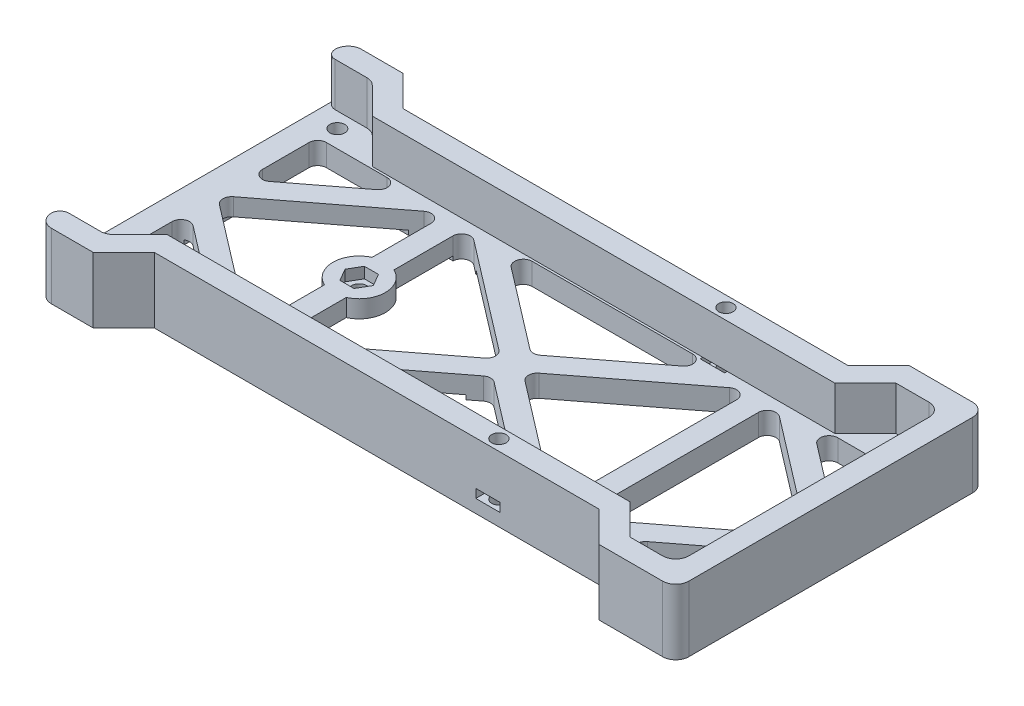
SolidWorks part; units mm, degrees
material "ABS PC"
ref_plane "Front Plane" through (0, 0, 0) normal (0, 0, 1) x (1, 0, 0)
ref_plane "Top Plane" through (0, 0, 0) normal (0, 1, 0) x (1, 0, 0)
ref_plane "Right Plane" through (0, 0, 0) normal (1, 0, 0) x (0, 0, -1)
sketch "Sketch1" plane through (0, 0, 0) normal (0, 1, 0) x (1, 0, 0)
  line L1 (73, -35.5) -> (-73, -35.5)
  line L2 (73, -35.5) -> (73, 35.5)
  line L3 (73, 35.5) -> (-73, 35.5)
  line L4 (-73, -35.5) -> (-73, 35.5)
  line L5 (73, -35.5) -> (-73, 35.5) construction
  line L6 (73, 35.5) -> (-73, -35.5) construction
  point P0 (0, 0)
  dimension "D1" = 146
  dimension "D2" = 71
extrude "Boss-Extrude1" add sketch "Sketch1" along normal blind 15
shell "Shell1" thickness 5 removed face at (0, 15, 0)
sketch "Sketch2" plane through (0, 15, 0) normal (0, 1, 0) x (1, 0, 0)
  line L0 (-73, 35.5) -> (-73, -35.5) construction
  line L1 (-68, 30.5) -> (-73, 30.5)
  line L2 (-68, 30.5) -> (-68, -30.5)
  line L3 (-68, -30.5) -> (-73, -30.5)
  line L4 (-73, 30.5) -> (-73, -30.5)
extrude "Cut-Extrude1" cut sketch "Sketch2" against normal up to surface (10 mm away) up to face at (0, 5, 0)
sketch "Sketch3" plane through (0, 5, 0) normal (0, 1, 0) x (1, 0, 0)
  line L0 (-29.7548, 0) -> (34.5948, 0) construction
  line L1 (-2.5, 23.5) -> (-2.5, 30.5) construction
  line L2 (68, 30.5) -> (-73, 30.5) construction
  line L3 (-55.5, 23.5) -> (50.5, 23.5)
  line L4 (50.5, 23.5) -> (57.5, 30.5)
  line L5 (57.5, 30.5) -> (-62.5, 30.5)
  line L6 (-55.5, 23.5) -> (-62.5, 30.5)
  line L7 (-55.5, -23.5) -> (-62.5, -30.5)
  line L8 (57.5, -30.5) -> (-62.5, -30.5)
  line L9 (50.5, -23.5) -> (57.5, -30.5)
  line L10 (-55.5, -23.5) -> (50.5, -23.5)
  dimension "D1" = 7
  dimension "D2" = 120
  dimension "D3" = 45
extrude "Boss-Extrude2" add sketch "Sketch3" along normal up to surface (10 mm away) up to face at (-1.25, 15, 0)
hole_wizard "CSK for M3 Flat Head Machine Screw1" positions "Sketch5" profile "Sketch6" countersink size "M3" standard "ANSI Metric"
sketch "Sketch5" plane through (0, 0, 0) normal (0, -1, 0) x (-1, 0, 0)
  line L1 (67, 27) -> (-63, 27)
  line L2 (67, 27) -> (67, -27)
  line L3 (67, -27) -> (-63, -27)
  line L4 (-63, 27) -> (-63, -27)
  line L5 (67, 27) -> (-63, -27) construction
  line L6 (67, -27) -> (-63, 27) construction
  line L7 (0, 0) -> (2, 0) construction
  point P2 (-63, -27)
  point P5 (67, 27)
  point P6 (67, -27)
  point P7 (-63, 27)
  dimension "D1" = 130
  dimension "D2" = 54
  dimension "D3" = 2
sketch "Sketch6" plane through (63, 0, 27) normal (1, 0, 0) x (0, 0, -1)
  line L0 (0, 0) -> (0, 11.0215)
  line L1 (0, 11.0215) -> (1.7, 10)
  line L2 (1.7, 10) -> (1.7, 1.45)
  line L3 (1.7, 1.45) -> (3.15, 0)
  line L5 (3.15, 0) -> (0, 0)
  line L6 (-1.7, 1.45) -> (-3.15, 0) construction
  line L10 (0, 11.0215) -> (-1.7, 10) construction
  line L11 (0, -6.35) -> (0, 107.95) construction
  dimension "Hole Dia." = 3.4
  dimension "Hole Depth" = 10
  dimension "Near C'Sink Dia." = 6.3
  dimension "Near C'Sink Angle" = 90
  dimension "Drill Angle" = 118
fillet "Fillet1" radius 3 4 edges at (-73, 7.5, 35.5) (73, 7.5, 35.5) (-73, 7.5, -35.5) (73, 7.5, -35.5)
sketch "Sketch7" plane through (0, 0, 0) normal (0, -1, 0) x (1, 0, 0)
  circle A0 centre (-67, 27) radius 3.5
  circle A1 centre (-67, -27) radius 3.5
  circle A2 centre (63, -27) radius 3.5
  circle A3 centre (63, 27) radius 3.5
  dimension "D1" = 7
extrude "Cut-Extrude2" [suppressed] cut sketch "Sketch7" against normal blind 3
sketch "Sketch8" plane through (0, 0, 0) normal (0, -1, 0) x (1, 0, 0)
  line L0 (67.5, 0) -> (37.5, 0) construction
  line L1 (67.5, 0) -> (37.5, 23)
  line L2 (37.5, 23) -> (37.5, -23)
  line L3 (67.5, 0) -> (37.5, -23)
  line L4 (0, 4.3837) -> (24.2821, 23)
  line L5 (35, 20.6198) -> (35, -36.8998) construction
  line L6 (2.5, 0) -> (32.5, -23)
  line L7 (32.5, 23) -> (32.5, -23)
  line L8 (2.5, 0) -> (32.5, 23)
  line L9 (0, 35.5) -> (0, -35.5) construction
  line L10 (-70, 35.5) -> (70, 35.5) construction
  line L11 (70, -35.5) -> (-70, -35.5) construction
  line L12 (-2.5, 0) -> (-32.5, 23)
  line L13 (-32.5, 23) -> (-32.5, -23)
  line L14 (-2.5, 0) -> (-32.5, -23)
  line L15 (-67.5, 0) -> (-37.5, -23)
  line L16 (-37.5, 23) -> (-37.5, -23)
  line L17 (-67.5, 0) -> (-37.5, 23)
  line L19 (0, 4.3837) -> (-24.2821, 23)
  line L20 (-24.2821, 23) -> (24.2821, 23)
  line L21 (-45.7179, 23) -> (-67.5, 23)
  line L22 (-67.5, 23) -> (-67.5, 6.3004)
  line L23 (-67.5, 6.3004) -> (-45.7179, 23)
  line L24 (67.5, 6.3004) -> (45.7179, 23)
  line L25 (67.5, 23) -> (67.5, 6.3004)
  line L26 (45.7179, 23) -> (67.5, 23)
  line L27 (45.7179, -23) -> (67.5, -23)
  line L28 (67.5, -23) -> (67.5, -6.3004)
  line L29 (67.5, -6.3004) -> (45.7179, -23)
  line L30 (-67.5, -6.3004) -> (-45.7179, -23)
  line L31 (-67.5, -23) -> (-67.5, -6.3004)
  line L32 (-45.7179, -23) -> (-67.5, -23)
  line L33 (-24.2821, -23) -> (24.2821, -23)
  line L34 (0, -4.3837) -> (-24.2821, -23)
  line L35 (0, -4.3837) -> (24.2821, -23)
  point P31 (0, 23)
  dimension "D1" = 46
  dimension "D2" = 5
  dimension "D3" = 30
  dimension "D4" = 5
  dimension "D5" = 5
  dimension "D6" = 5
extrude "Cut-Extrude3" cut sketch "Sketch8" against normal blind 10
fillet "Fillet2" radius 2 30 edges at (-37.5, 2.5, -23) (-67.5, 2.5, 0) (-37.5, 2.5, 23) (-32.5, 2.5, -23) (-2.5, 2.5, 0) (-32.5, 2.5, 23) (32.5, 2.5, -23) (2.5, 2.5, 0) (32.5, 2.5, 23) (37.5, 2.5, -23) (37.5, 2.5, 23) (67.5, 2.5, 0) (67.5, 2.5, 6.3004) (45.7179, 2.5, 23) (67.5, 2.5, 23) (67.5, 2.5, -6.3004) (67.5, 2.5, -23) (45.7179, 2.5, -23) (-67.5, 2.5, -6.3004) (-45.7179, 2.5, -23) (-67.5, 2.5, -23) (-67.5, 2.5, 6.3004) (-45.7179, 2.5, 23) (-67.5, 2.5, 23) (0, 2.5, -4.3837) (24.2821, 2.5, -23) (-24.2821, 2.5, -23) (24.2821, 2.5, 23) (0, 2.5, 4.3837) (-24.2821, 2.5, 23)
sketch "Sketch9" plane through (0, 5, 0) normal (0, 1, 0) x (1, 0, 0)
  circle A0 centre (0, 0) radius 6
  dimension "D1" = 12
extrude "Boss-Extrude3" [suppressed] add sketch "Sketch9" against normal through all
hole_wizard "Ø4.0 (4) Diameter Hole1" [suppressed] positions "Sketch10" profile "Sketch11" hole size "Ø4.0" standard "ANSI Metric"
sketch "Sketch10" plane through (0, 5, 0) normal (0, 1, 0) x (1, 0, 0)
  point P0 (0, 0)
sketch "Sketch11" plane through (0, 5, 0) normal (1, 0, 0) x (0, 0, 1)
  line L0 (0, 0) -> (0, 11.2017)
  line L1 (0, 11.2017) -> (2, 10)
  line L2 (2, 10) -> (2, 0)
  line L5 (2, 0) -> (0, 0)
  line L10 (0, 11.2017) -> (-2, 10) construction
  line L11 (0, -6.35) -> (0, 107.95) construction
  dimension "Hole Dia." = 4
  dimension "Hole Depth" = 10
  dimension "Drill Angle" = 118
sketch "Sketch12" plane through (0, 5, 0) normal (0, 1, 0) x (1, 0, 0)
  line L1 (3.2332, 0) -> (1.6166, 2.8)
  line L2 (1.6166, 2.8) -> (-1.6166, 2.8)
  line L3 (-1.6166, 2.8) -> (-3.2332, 0)
  line L4 (-3.2332, 0) -> (-1.6166, -2.8)
  line L5 (-1.6166, -2.8) -> (1.6166, -2.8)
  line L6 (1.6166, -2.8) -> (3.2332, 0)
  circle A0 centre (0, 0) radius 2.8 construction
  dimension "D1" = 5.6
extrude "Cut-Extrude4" [suppressed] cut sketch "Sketch12" against normal blind 3
sketch "Sketch13" plane through (0, 0, 0) normal (0, -1, 0) x (1, 0, 0)
  line L0 (70, -35.5) -> (-70, -35.5) construction
  line L1 (-29, -25.5) -> (-41, -25.5)
  line L2 (-29, -25.5) -> (-29, -33.5)
  line L3 (-29, -33.5) -> (-41, -33.5)
  line L4 (-41, -25.5) -> (-41, -33.5)
  line L5 (-29, -25.5) -> (-41, -33.5) construction
  line L6 (-29, -33.5) -> (-41, -25.5) construction
  line L7 (-35, -29.5) -> (-35, -9.4194) construction
  line L8 (-32.5, -9.4194) -> (-37.5, -9.4194) construction
  line L9 (-37.5, -18.9465) -> (-37.5, 18.9465) construction
  line L10 (-32.5, 18.9465) -> (-32.5, -18.9465) construction
  point P0 (-35, -29.5)
  point P15 (-35, -9.4194)
  dimension "D1" = 12
  dimension "D2" = 8
  dimension "D3" = 2
extrude "Cut-Extrude5" [suppressed] cut sketch "Sketch13" against normal through all
fillet "Fillet3" [suppressed] radius 2
sketch "Sketch14" plane through (0, 5, 0) normal (0, 1, 0) x (1, 0, 0)
  line L0 (-35, 0) -> (0, 0) construction
  line L1 (-32.5, 0) -> (-37.5, 0) construction
  line L2 (-37.5, -18.9465) -> (-37.5, 18.9465) construction
  line L3 (-32.5, 18.9465) -> (-32.5, -18.9465) construction
  circle A0 centre (-35, 0) radius 6
  point P9 (-35, 0)
  dimension "D1" = 12
extrude "Boss-Extrude4" add sketch "Sketch14" against normal through all
hole_wizard "Ø3.5 (3.5) Diameter Hole1" positions "Sketch15" profile "Sketch16" hole size "Ø3.5" standard "ANSI Metric" end condition through all
sketch "Sketch15" plane through (0, 5, 0) normal (0, 1, 0) x (1, 0, 0)
  point P0 (-35, 0)
sketch "Sketch16" plane through (-35, 5, 0) normal (1, 0, 0) x (0, 0, 1)
  line L0 (0, 0) -> (0, 5)
  line L1 (0, 5) -> (1.75, 5)
  line L2 (1.75, 5) -> (1.75, 0)
  line L5 (1.75, 0) -> (0, 0)
  line L11 (0, -6.35) -> (0, 107.95) construction
  dimension "Thru Hole Dia." = 3.5
  dimension "Thru Hole Depth" = 5
sketch "Sketch17" plane through (0, 5, 0) normal (0, 1, 0) x (1, 0, 0)
  line L1 (-31.7668, 0) -> (-33.3834, 2.8)
  line L2 (-33.3834, 2.8) -> (-36.6166, 2.8)
  line L3 (-36.6166, 2.8) -> (-38.2332, 0)
  line L4 (-38.2332, 0) -> (-36.6166, -2.8)
  line L5 (-36.6166, -2.8) -> (-33.3834, -2.8)
  line L6 (-33.3834, -2.8) -> (-31.7668, 0)
  circle A0 centre (-35, 0) radius 2.8 construction
  dimension "D1" = 5.6
extrude "Cut-Extrude6" cut sketch "Sketch17" against normal blind 2.5
sketch "Sketch19" plane through (0, 0, 0) normal (0, -1, 0) x (1, 0, 0)
  line L1 (-66.5, -19) -> (-3.5, -19)
  line L2 (-66.5, -19) -> (-66.5, 19)
  line L3 (-66.5, 19) -> (-3.5, 19)
  line L4 (-3.5, -19) -> (-3.5, 19)
  line L5 (-66.5, -19) -> (-3.5, 19) construction
  line L6 (-66.5, 19) -> (-3.5, -19) construction
  point P0 (-35, 0)
  dimension "D1" = 63
  dimension "D2" = 38
extrude "Cut-Extrude7" cut sketch "Sketch19" against normal blind 1 and the other way blind 10
chamfer "Chamfer1" [suppressed] distance 1 angle 45
sketch "Sketch20" plane through (0, 15, 0) normal (0, 1, 0) x (1, 0, 0)
  line L0 (-58.9645, 34.0355) -> (-60.4289, 35.5)
  line L1 (70, 35.5) -> (-70, 35.5) construction
  line L2 (53.9645, 34.0355) -> (55.4289, 35.5)
  line L3 (-60.4289, 35.5) -> (55.4289, 35.5)
  line L4 (-58.9645, -34.0355) -> (-53.4289, -28.5)
  line L5 (-53.4289, -28.5) -> (48.4289, -28.5)
  line L6 (-15.2467, 0) -> (14.0675, 0) construction
  line L7 (48.4289, -28.5) -> (53.9645, -34.0355)
  line L8 (-60.4289, -35.5) -> (55.4289, -35.5)
  line L9 (48.4289, 28.5) -> (53.9645, 34.0355)
  line L10 (-53.4289, 28.5) -> (48.4289, 28.5)
  line L11 (-58.9645, 34.0355) -> (-53.4289, 28.5)
  line L12 (48.4289, 28.5) -> (53.9645, 34.0355)
  line L13 (-53.4289, 28.5) -> (48.4289, 28.5)
  line L14 (-58.9645, 34.0355) -> (-53.4289, 28.5)
  line L15 (53.9645, -34.0355) -> (55.4289, -35.5)
  line L16 (-58.9645, -34.0355) -> (-60.4289, -35.5)
  dimension "D1" = 5
extrude "Cut-Extrude8" cut sketch "Sketch20" against normal through all
fillet "Fillet4" radius 2 2 edges at (-73, 10, -30.5) (-73, 10, 30.5)
fillet "Fillet5" radius 3 4 edges at (-62.5, 10, -30.5) (-62.5, 10, 30.5) (68, 10, 30.5) (68, 10, -30.5)
hole_wizard "Ø3.3 (3.3) Diameter Hole1" positions "Sketch22" profile "Sketch23" hole size "Ø3.3" standard "ANSI Metric" end condition through all
sketch "Sketch22" plane through (0, 0, 0) normal (0, -1, 0) x (-1, 0, 0)
  line L0 (-32.5, 0) -> (-37.5, 0) construction
  line L1 (-32.5, 18.9465) -> (-32.5, -18.9465) construction
  line L2 (-37.5, -18.9465) -> (-37.5, 18.9465) construction
  line L4 (-35, 0) -> (-35, -23.5) construction
  line L8 (-23, -28.5) -> (-23, -23.5) construction
  line L9 (-48.4289, -28.5) -> (53.4289, -28.5) construction
  line L10 (-50.5, -23.5) -> (55.5, -23.5) construction
  line L12 (-23, 23.5) -> (-23, 28.5) construction
  line L13 (55.5, 23.5) -> (-50.5, 23.5) construction
  line L14 (53.4289, 28.5) -> (-48.4289, 28.5) construction
  point P23 (-23, -26)
  point P28 (-23, 26)
  dimension "D1" = 12
sketch "Sketch23" plane through (23, 0, -26) normal (1, 0, 0) x (0, 0, -1)
  line L0 (0, 0) -> (0, 15)
  line L1 (0, 15) -> (1.65, 15)
  line L2 (1.65, 15) -> (1.65, 0)
  line L5 (1.65, 0) -> (0, 0)
  line L11 (0, -6.35) -> (0, 107.95) construction
  dimension "Thru Hole Dia." = 3.3
  dimension "Thru Hole Depth" = 15
sketch "Sketch24" plane through (0, 0, 28.5) normal (0, 0, 1) x (1, 0, 0)
  line L0 (21.35, 4) -> (24.65, 4) construction
  line L1 (21.35, 15) -> (21.35, 0) construction
  line L2 (24.65, 0) -> (24.65, 15) construction
  line L3 (48.4289, 0) -> (-53.4289, 0) construction
  line L4 (25.8, 3) -> (20.2, 3)
  line L5 (25.8, 3) -> (25.8, 5)
  line L6 (25.8, 5) -> (20.2, 5)
  line L7 (20.2, 3) -> (20.2, 5)
  line L8 (25.8, 3) -> (20.2, 5) construction
  line L9 (25.8, 5) -> (20.2, 3) construction
  point P6 (23, 4)
  dimension "D1" = 2
  dimension "D2" = 5.6
  dimension "D3" = 3
extrude "Cut-Extrude9" cut sketch "Sketch24" against normal blind 5.6
sketch "Sketch25" plane through (0, 0, -28.5) normal (0, 0, -1) x (-1, 0, 0)
  line L0 (-24.65, 4) -> (-21.35, 4) construction
  line L1 (-24.65, 15) -> (-24.65, 0) construction
  line L2 (-21.35, 0) -> (-21.35, 15) construction
  line L3 (53.4289, 0) -> (-48.4289, 0) construction
  line L4 (-20.2, 3) -> (-25.8, 3)
  line L5 (-20.2, 3) -> (-20.2, 5)
  line L6 (-20.2, 5) -> (-25.8, 5)
  line L7 (-25.8, 3) -> (-25.8, 5)
  line L8 (-20.2, 3) -> (-25.8, 5) construction
  line L9 (-20.2, 5) -> (-25.8, 3) construction
  point P6 (-23, 4)
  dimension "D1" = 5.6
  dimension "D2" = 2
  dimension "D3" = 3
extrude "Cut-Extrude10" cut sketch "Sketch25" against normal blind 5.6
